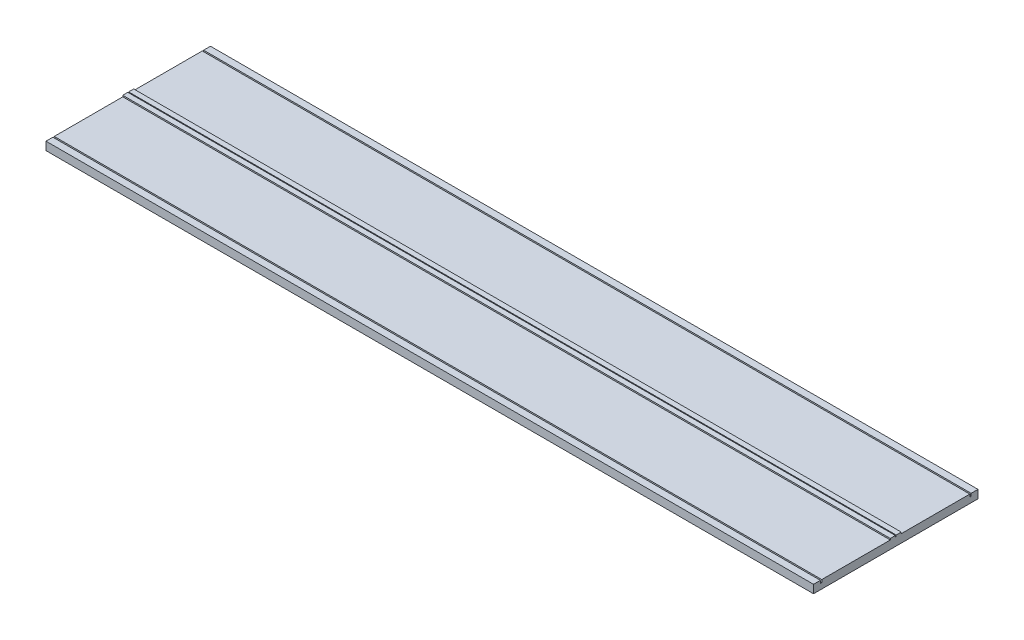
SolidWorks part; units mm, degrees
ref_plane "Front Plane" through (0, 0, 0) normal (0, 0, 1) x (1, 0, 0)
ref_plane "Top Plane" through (0, 0, 0) normal (0, 1, 0) x (1, 0, 0)
ref_plane "Right Plane" through (0, 0, 0) normal (1, 0, 0) x (0, 0, -1)
sketch "Sketch1" plane through (0, 0, 0) normal (0, 1, 0) x (1, 0, 0)
  line L0 (-140, 0) -> (140, 0)
  line L1 (-140, -30) -> (140, -30)
  line L2 (-140, -30) -> (-140, 30)
  line L3 (-140, 30) -> (140, 30)
  line L4 (140, -30) -> (140, 30)
  line L5 (-140, -30) -> (140, 30) construction
  line L6 (-140, 30) -> (140, -30) construction
  line L7 (-140, 0) -> (-140, 2)
  line L8 (140, 0) -> (140, 2)
  line L9 (-140, 2) -> (140, 2)
  line L10 (-140, -2) -> (140, -2)
  line L11 (-140, 0) -> (-140, -2)
  line L12 (140, 0) -> (140, -2)
  line L13 (-140, -27) -> (140, -27)
  line L14 (-140, -27.5) -> (140, -27.5)
  line L15 (140, -27.5) -> (140, -27)
  line L16 (-140, 27.5) -> (140, 27.5)
  line L17 (-140, 27) -> (140, 27)
  line L18 (-140, 27.5) -> (-140, 27)
  line L19 (140, 27.5) -> (140, 27)
  point P0 (0, 0)
  dimension "D1" = 280
  dimension "D2" = 60
  dimension "D3" = 2
  dimension "D4" = 2
  dimension "D5" = 3
  dimension "D6" = 0.5
extrude "Boss-Extrude1" add sketch "Sketch1" against normal blind 3 contours L2 L3 L4 L1
extrude "Cut-Extrude1" cut sketch "Sketch1<9>" against normal blind 1 contours L16 L19 L17 L18
sketch "Sketch1<9>" plane through (0, 0, 0) normal (0, 1, 0) x (1, 0, 0) same geometry as "Sketch1"
mirror "Mirror1" about plane through (0, 0, 0) normal (0, 0, 1) of "Cut-Extrude1"
ref_plane "Plane1" through (140, 0, 0) normal (1, 0, 0) x (0, 0, -1)
sketch "Sketch2" plane through (140, 0, 0) normal (1, 0, 0) x (0, 0, -1)
  line L0 (0, 0) -> (0, 0.5)
  line L1 (0, 0.5) -> (2, 0.5)
  line L2 (2, 0.5) -> (2, 0)
  line L3 (0, 0) -> (2, 0) construction
  line L4 (30, 0) -> (-30, 0) construction
  line L5 (-2, 0) -> (2, 0)
  line L6 (0, 0.5) -> (-2, 0.5)
  line L7 (-2, 0.5) -> (-2, 0)
  line L8 (0, 0) -> (-2, 0) construction
  dimension "D1" = 0.5
extrude "Boss-Extrude2" add sketch "Sketch2" against normal blind 280 contours L6 L7 L5 L2 L1
sketch "Sketch3" plane through (140, 0, 0) normal (1, 0, 0) x (0, 0, -1)
  line L0 (0, 0.5) -> (0.15, 0.5)
  line L1 (2, 0.5) -> (-2, 0.5) construction
  line L2 (0.15, 0.5) -> (0.15, 0)
  line L3 (0, 0) -> (2, 0) construction
  line L4 (0.15, 0) -> (0, 0)
  line L5 (0, 0) -> (0, 0.5)
  line L6 (-0.15, 0.5) -> (-0.15, 0)
  line L7 (-0.15, 0.5) -> (0, 0.5)
  line L8 (-0.15, 0) -> (0, 0)
  line L9 (-0.15, 0.5) -> (0, 0.5)
  dimension "D1" = 0.15
extrude "Cut-Extrude5" cut sketch "Sketch3" against normal blind 280 contours L5 L4 L2 L0 | L6 L8 L5 L7 region at (140, 0.25, -0.075) region at (140, 0.25, 0.075)
